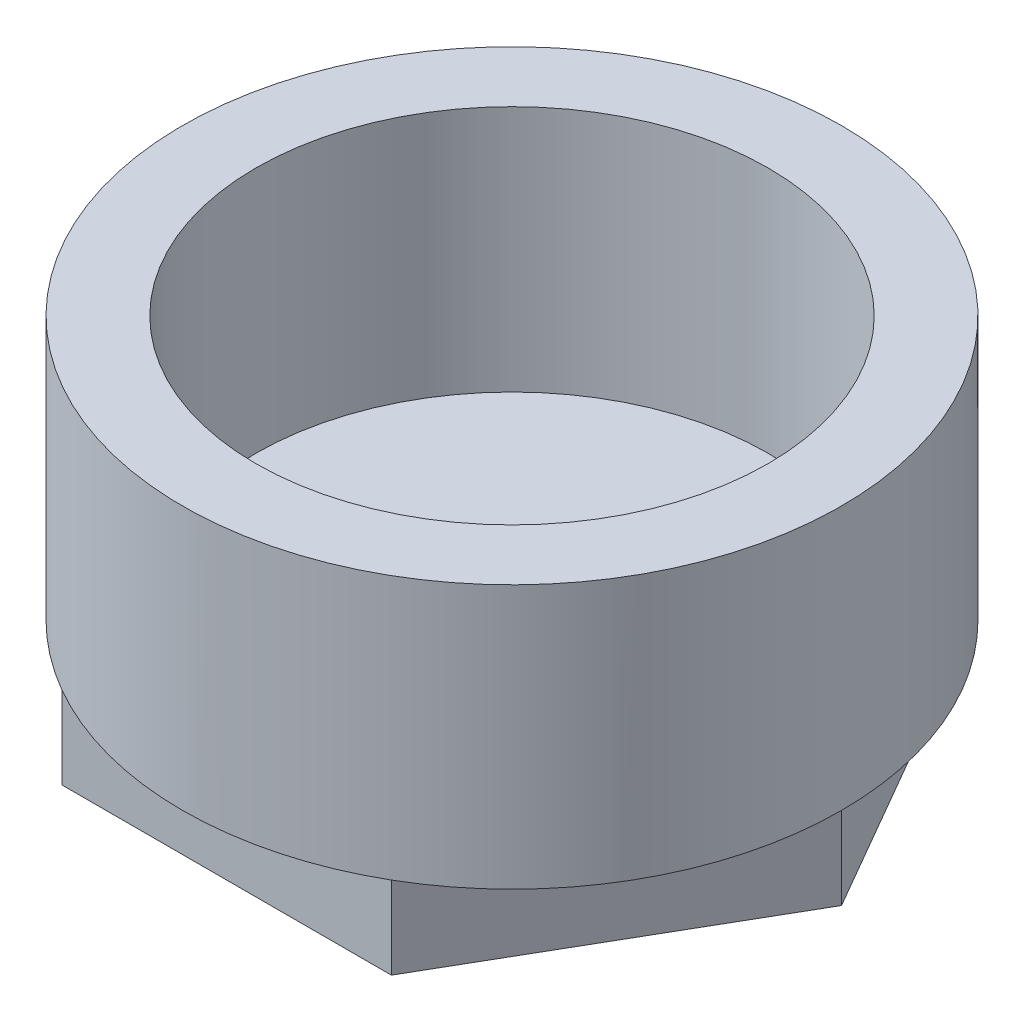
SolidWorks part; units mm, degrees
material "Plain Carbon Steel"
ref_plane "Piano frontale" through (0, 0, 0) normal (0, 0, 1) x (1, 0, 0)
ref_plane "Piano superiore" through (0, 0, 0) normal (0, 1, 0) x (1, 0, 0)
ref_plane "Piano destro" through (0, 0, 0) normal (1, 0, 0) x (0, 0, -1)
sketch "Schizzo1" plane through (0, 0, 0) normal (0, 0, 1) x (1, 0, 0)
  line L0 (0, 0) -> (-20, 0)
  line L1 (-20, 0) -> (-20, 21)
  line L2 (-20, 21) -> (-15.5465, 21)
  line L3 (-15.5465, 21) -> (-15.5465, 6)
  line L4 (-15.5465, 6) -> (0, 6)
  line L5 (0, 6) -> (0, 0)
  line L6 (0, 0) -> (0, 10.8439) construction
  dimension "D1" = 40
  dimension "D2" = 31.093
  dimension "D3" = 15
  dimension "D4" = 21
revolve "Rivoluzione1" add sketch "Schizzo1" angle 360 about L6
sketch "Schizzo2" plane through (0, 0, 0) normal (0, -1, 0) x (1, 0, 0)
  line L1 (0, 0) -> (10, 0) construction
  circle A0 centre (0, 0) radius 3.175
  circle A1 centre (10, 0) radius 0.5
  dimension "D1" = 6.35
  dimension "D2" = 1
  dimension "D3" = 10
extrude "Taglio-Estrusione1" cut sketch "Schizzo2" against normal blind 10
sketch "Schizzo3" plane through (0, 0, 0) normal (0, -1, 0) x (1, 0, 0)
  circle A0 centre (0, 0) radius 1.019
  circle A1 centre (0, 0) radius 1.5875
  dimension "D1" = 3.175
extrude "Estrusione-Estrusione1" [suppressed] add sketch "Schizzo3" along normal blind 8
sketch "Schizzo4" plane through (0, 0, 0) normal (0, 0, 1) x (1, 0, 0)
  line L0 (0, 0) -> (0, -9.8437)
sketch "Schizzo5" plane through (0, 0, 0) normal (0, -1, 0) x (-1, 0, 0)
  line L0 (10, 17.3205) -> (20, 0)
  line L1 (20, 0) -> (10, -17.3205)
  line L2 (10, -17.3205) -> (-10, -17.3205)
  line L3 (-10, -17.3205) -> (-20, 0)
  line L4 (-20, 0) -> (-10, 17.3205)
  line L5 (-10, 17.3205) -> (10, 17.3205)
  line L6 (-8.5, 0) -> (0, 0) construction
  circle A0 centre (0, 0) radius 20 construction
  circle A1 centre (0, 0) radius 15
  circle A2 centre (-8.5, 0) radius 0.5
  circle M9 centre (0, 0) radius 20
  dimension "D1" = 1
  dimension "D2" = 8.5
extrude "Taglio-Estrusione2" cut sketch "Schizzo5" against normal blind 5 contours L5 M9 | L0 M9 | L1 M9 | L2 M9 | L3 M9 | L4 M9 region at (-15.9337, 0, -9.1994) region at (0, 0, -18.3987) region at (-15.9337, 0, 9.1994) region at (15.9337, 0, -9.1994) region at (0, 0, 18.3987) region at (15.9337, 0, 9.1994)
